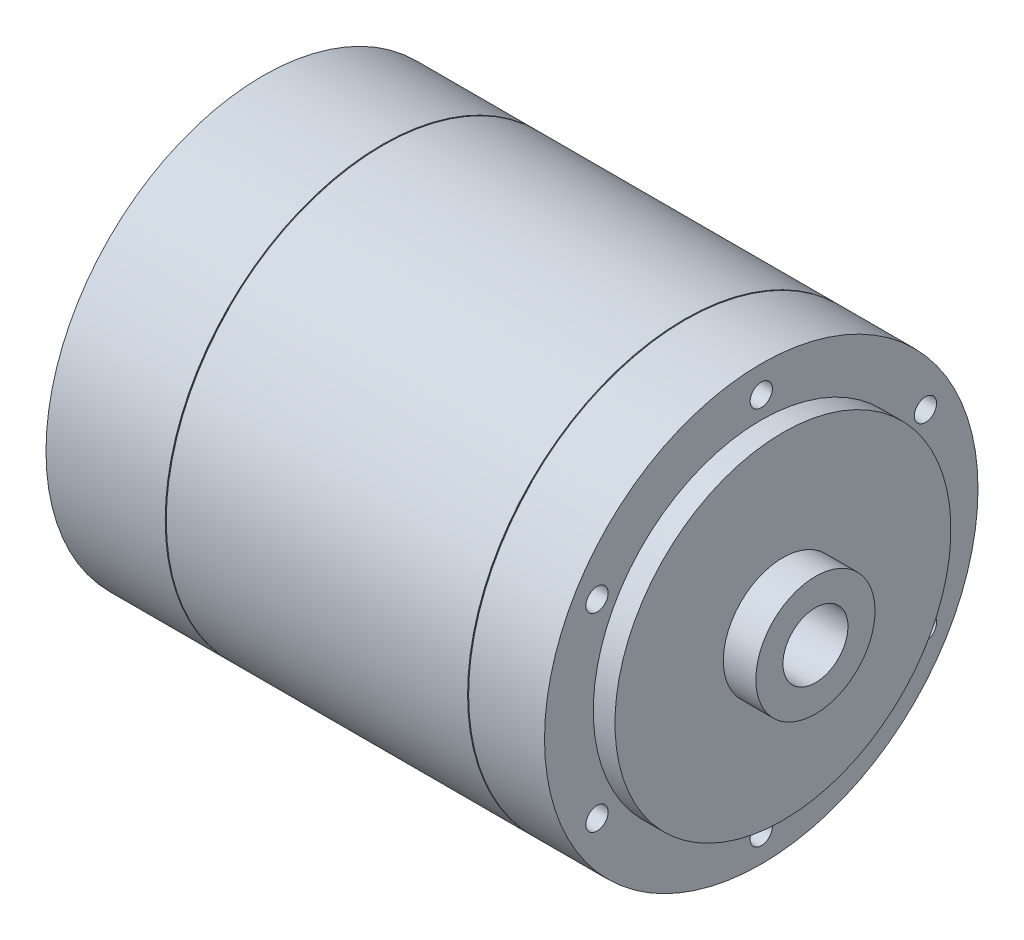
SolidWorks part; units mm, degrees
material "Acier non allié"
ref_plane "Plan1" through (0, 0, 0) normal (0, 0, 1) x (1, 0, 0)
ref_plane "Plan2" through (0, 0, 0) normal (0, 1, 0) x (1, 0, 0)
ref_plane "Plan3" through (0, 0, 0) normal (1, 0, 0) x (0, 0, -1)
sketch "Esquisse1" plane through (0, 0, 0) normal (0, 0, 1) x (1, 0, 0)
  line L0 (-54, 5) -> (-54, 12)
  line L1 (-54, 12) -> (-51, 12)
  line L2 (-51, 12) -> (-51, 20)
  line L3 (-51, 20) -> (-40, 20)
  line L4 (-40, 20) -> (-40, 19.9)
  line L5 (-40, 19.9) -> (-39.9, 19.9)
  line L6 (-39.9, 19.9) -> (-39.9, 20)
  line L7 (-39.9, 20) -> (-12.1, 20)
  line L8 (-12.1, 20) -> (-12.1, 19.9)
  line L9 (-12.1, 19.9) -> (-12, 19.9)
  line L10 (-12, 19.9) -> (-12, 20)
  line L11 (-12, 20) -> (-5, 20)
  line L12 (-5, 20) -> (-5, 15.5)
  line L13 (-92, 0) -> (31.2, 0) construction
  line L14 (-5, 15.5) -> (-3, 15.5)
  line L15 (-3, 15.5) -> (-3, 5.5)
  line L16 (-3, 5.5) -> (0, 5.5)
  line L17 (0, 5.5) -> (0, 0)
  line L18 (-54, 5) -> (-52, 5)
  line L19 (-52, 5) -> (-52, 0)
  line L20 (-52, 0) -> (0, 0)
  dimension "D1" = 3
  dimension "D2" = 12
  dimension "D3" = 20
  dimension "D4" = 0.1
  dimension "D5" = 0.1
  dimension "D6" = 0.1
  dimension "D7" = 0.1
  dimension "D8" = 20
  dimension "D9" = 20
  dimension "D10" = 7
  dimension "D11" = 11
  dimension "D12" = 2
  dimension "D13" = 15.5
  dimension "D14" = 3
  dimension "D15" = 5.5
  dimension "D16" = 51
  dimension "D17" = 5
  dimension "D18" = 2
revolve "Base-Révolution" add sketch "Esquisse1" angle 360 about L13
shell "Coque1" thickness 5
chamfer "Chanfrein1" distance 0.5 angle 45 1 edges at (-54, -12, 0)
sketch "Esquisse5" plane through (0, 0, 0) normal (1, 0, 0) x (0, 0, -1)
  circle A0 centre (0, 0) radius 3
  dimension "D1" = 6
extrude "Enlèv. mat.-Extru.1" cut sketch "Esquisse5" against normal up to next
hole_wizard "Trou taraudé M41" positions "Esquisse3" profile "Esquisse4" tap size "M4" standard "ISO"
sketch "Esquisse3" plane through (-51, 0, 0) normal (-1, 0, 0) x (0, 0, 1)
  point P0 (0, 17.5)
  dimension "D1" = 17.5
cosmetic thread "Représentation de filetage1" parameters "D1"=8, "D2"=4
sketch "Esquisse4" plane through (-51, 17.5, 0) normal (0, 1, 0) x (0, 0, 1)
  line L0 (0, 0) -> (0, 12.4526)
  line L1 (0, 12.4526) -> (1.65, 11.5)
  line L2 (1.65, 11.5) -> (1.65, 0)
  line L5 (1.65, 0) -> (0, 0)
  line L10 (0, 12.4526) -> (-1.65, 11.5) construction
  line L11 (0, -6.35) -> (0, 107.95) construction
  dimension "Diamètre du trou pour taraudage" = 3.3
  dimension "Profondeur du trou pour taraudage" = 11.5
  dimension "Angle de pointe" = 120
hole_wizard "Trou taraudé M2.51" positions "Esquisse7" profile "Esquisse6" tap size "M2.5" standard "ISO"
sketch "Esquisse7" plane through (-5, 0, 0) normal (1, 0, 0) x (0, 0, -1)
  point P0 (0, 17.5)
  dimension "D1" = 17.5
sketch "Esquisse6" plane through (-5, 17.5, 0) normal (0, 1, 0) x (0, 0, -1)
  line L0 (0, 0) -> (0, 20.5918)
  line L1 (0, 20.5918) -> (1.025, 20)
  line L2 (1.025, 20) -> (1.025, 0)
  line L5 (1.025, 0) -> (0, 0)
  line L10 (0, 20.5918) -> (-1.025, 20) construction
  line L11 (0, -6.35) -> (0, 107.95) construction
  dimension "Diamètre du trou pour taraudage" = 2.05
  dimension "Profondeur du trou pour taraudage" = 20
  dimension "Angle de pointe" = 120
cosmetic thread "Filetage de perçage1" parameters "D1"=17, "D2"=2.5
pattern_circular "Répétition circulaire1" count 8 every 45 about axis through (-92, 0, 0) along (1, 0, 0) of "Trou taraudé M41"
pattern_circular "Répétition circulaire2" count 6 every 60 about axis through (-92, 0, 0) along (1, 0, 0) of "Trou taraudé M2.51"
